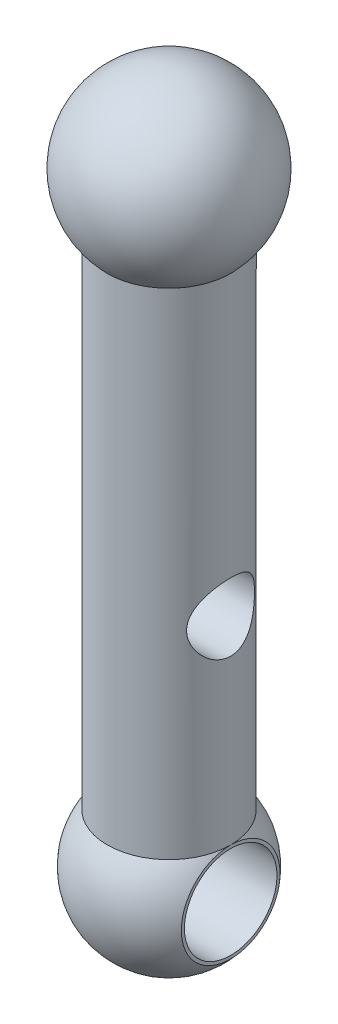
SolidWorks part; units mm, degrees
ref_plane "Front Plane" through (0, 0, 0) normal (0, 0, 1) x (1, 0, 0)
ref_plane "Top Plane" through (0, 0, 0) normal (0, 1, 0) x (1, 0, 0)
ref_plane "Right Plane" through (0, 0, 0) normal (1, 0, 0) x (0, 0, -1)
sketch "Sketch1" plane through (0, 0, 0) normal (0, 1, 0) x (1, 0, 0)
  line L0 (0, 0) -> (0, -5.08)
  line L1 (12.7, -5.08) -> (12.7, 0)
  line L2 (0, -5.08) -> (12.7, -5.08)
  arc A0 (0, 0) -> (12.7, 0) centre (6.35, -5.08) cw
  point P3 (0, 0)
  point P7 (0, 0)
  dimension "D1" = 12.7
  dimension "D2" = 5.08
revolve "Revolve1" add sketch "Sketch1" angle 360 about L2
sketch "Sketch3" plane through (0, 0, 0) normal (-1, 0, 0) x (0, 0, 1)
  circle A0 centre (5.08, 0) radius 4.7625
  circle A1 centre (5.08, 0) radius 5.08 construction
  dimension "D1" = 9.525
extrude "Cut-Extrude1" cut sketch "Sketch3" against normal blind 22.86
sketch "Sketch4" plane through (0, 0, 0) normal (0, 1, 0) x (1, 0, 0)
  circle A0 centre (6.35, -5.08) radius 6.35
  arc A2 (0, -10.16) -> (12.7, -10.16) centre (6.35, -5.08) ccw construction
  dimension "D1" = 12.7
extrude "Boss-Extrude1" add sketch "Sketch4" along normal blind 57.15 from offset 5.08
sketch "Sketch5" plane through (0, 62.23, 0) normal (0, 1, 0) x (1, 0, 0)
  line L0 (6.35, 3.81) -> (6.35, -13.97)
  arc A3 (6.35, -13.97) -> (6.35, 3.81) centre (6.35, -5.08) ccw
  dimension "D1" = 17.78
revolve "Revolve2" add sketch "Sketch5" angle 360 about L0
sketch "Sketch6" plane through (0, 0, 0) normal (1, 0, 0) x (0, 0, -1)
  line L0 (-5.08, 25.4) -> (-5.08, 0) construction
  circle A0 centre (-5.08, 25.4) radius 3.4925
  dimension "D1" = 6.985
  dimension "D2" = 25.4
extrude "Cut-Extrude2" cut sketch "Sketch6" along normal through all
